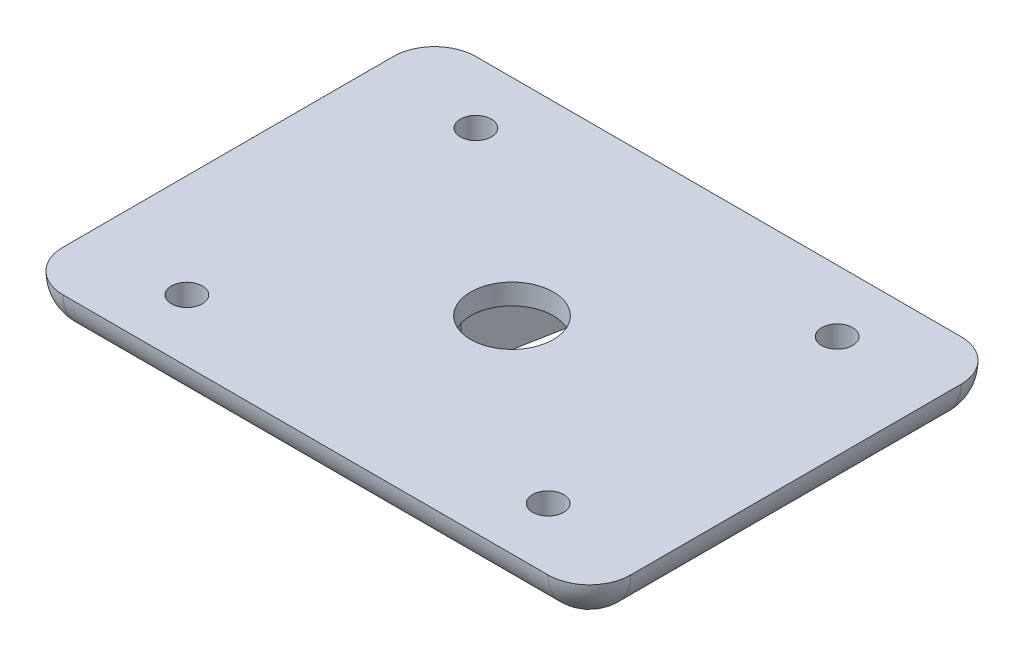
SolidWorks part; units mm, degrees
ref_plane "前视基准面" through (0, 0, 0) normal (0, 0, 1) x (1, 0, 0)
ref_plane "上视基准面" through (0, 0, 0) normal (0, 1, 0) x (1, 0, 0)
ref_plane "右视基准面" through (0, 0, 0) normal (1, 0, 0) x (0, 0, -1)
sketch "草图1" plane through (0, 0, 0) normal (0, 1, 0) x (1, 0, 0)
  line L1 (-27.5, 20) -> (27.5, 20)
  line L2 (-27.5, 20) -> (-27.5, -20)
  line L3 (-27.5, -20) -> (27.5, -20)
  line L4 (27.5, 20) -> (27.5, -20)
  circle A0 centre (0, 0) radius 4
  circle A1 centre (-17.5, 14) radius 1.5
  circle A2 centre (17.5, 14) radius 1.5
  circle A4 centre (17.5, -14) radius 1.5
  circle A5 centre (-17.5, -14) radius 1.5
  dimension "D5" = 8
  dimension "D6" = 3
  dimension "D9" = 6
  dimension "D11" = 6
  dimension "D1" = 40
  dimension "D2" = 55
  dimension "D3" = 27.5
  dimension "D4" = 20
  dimension "D7" = 6
  dimension "D8" = 10
  dimension "D10" = 10
extrude "凸台-拉伸1" add sketch "草图1" along normal blind 4 contours L1 L4 L3 L2
extrude "切除-拉伸5" cut sketch "草图1<6>" against normal blind 5 from surface flip side to cut starting at face at (0, 4, 0)
sketch "草图1<6>" plane through (0, 0, 0) normal (0, 1, 0) x (1, 0, 0) same geometry as "草图1"
fillet "圆角4" radius 4 1 edges at (27.5, 0, 0)
fillet "圆角6" radius 4 2 edges at (26.3284, 1.1716, 20) (-2, 0, 20)
fillet "圆角7" radius 4 2 edges at (-27.5, 1.1716, 18.8284) (-27.5, 0, -2)
fillet "圆角8" radius 4 3 edges at (-26.3284, 1.1716, -20) (26.3284, 1.1716, -20) (0, 0, -20)
sketch "草图2" plane through (0, 0, 0) normal (0, -1, 0) x (1, 0, 0)
  circle A0 centre (0, 0) radius 9.7056
extrude "凸台-拉伸2" add sketch "草图2" along normal blind 3 contours A0
sketch "草图3" plane through (0, -3, 0) normal (0, -1, 0) x (-1, 0, 0)
  line L0 (0, 0) -> (0, -13.7206) construction
  line L1 (3.2267, -9.1535) -> (4.9175, 0)
  line L2 (4.9175, 0) -> (3.2267, 9.1535)
  line L3 (-0.5382, 0) -> (15.8126, 0) construction
  line L4 (-3.9991, 0.0825) -> (-2.7214, 15.0874) construction
  line L5 (-4.9175, 0) -> (-3.2267, 9.1535)
  line L6 (-3.2267, -9.1535) -> (-4.9175, 0)
  circle A0 centre (0, 0) radius 9.7056 construction
  arc A1 (-3.2267, -9.1535) -> (3.2267, -9.1535) centre (0, 0) ccw
  circle A2 centre (0, 0) radius 9.7056
  arc A3 (3.2267, 9.1535) -> (-3.2267, 9.1535) centre (0, 0) ccw
  circle A4 centre (0, 0) radius 9.7056 construction
  dimension "D1" = 0
extrude "切除-拉伸7" cut sketch "草图3" against normal blind 5
sketch "草图4" plane through (0, 0, 0) normal (0, -1, 0) x (1, 0, 0)
  circle A0 centre (0.2437, -11.4789) radius 0.44
extrude "切除-拉伸8" cut sketch "草图4" against normal blind 2
sketch "草图5" plane through (0, 4, 0) normal (0, 1, 0) x (1, 0, 0)
  line L0 (17.5, -14) -> (-17.5, -14)
  line L1 (-17.5, -14) -> (-17.5, 14)
  line L2 (-17.5, 14) -> (17.5, 14)
  line L3 (17.5, 14) -> (17.5, -14)
  line L4 (17.5, 0) -> (-17.5, 0)
  line L5 (0, -14) -> (0, 14)
